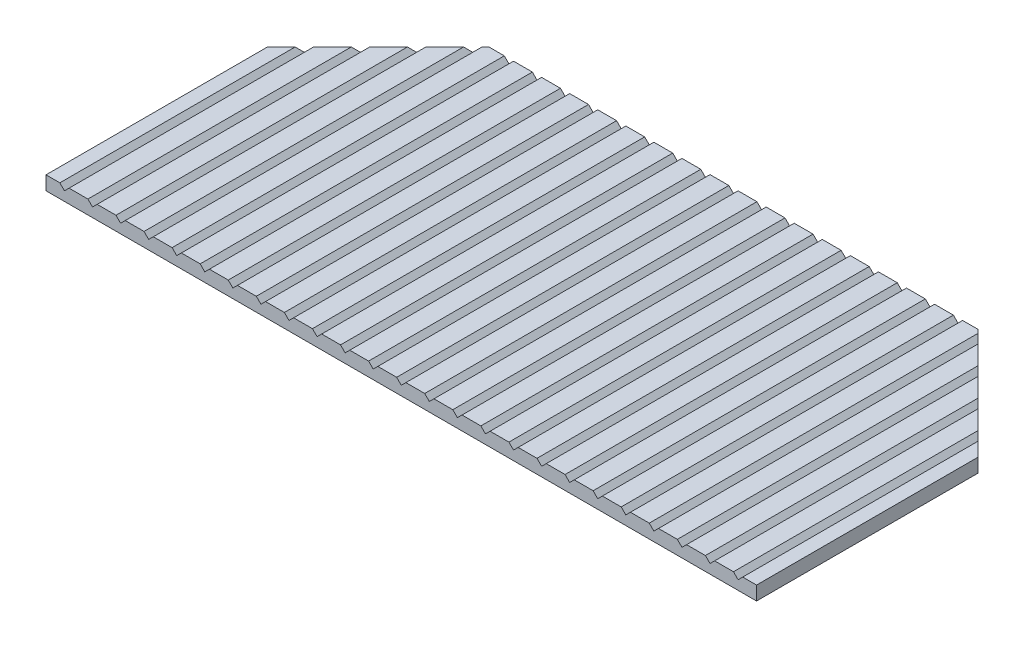
SolidWorks part; units mm, degrees
ref_plane "Front Plane" through (0, 0, 0) normal (0, 0, 1) x (1, 0, 0)
ref_plane "Top Plane" through (0, 0, 0) normal (0, 1, 0) x (1, 0, 0)
ref_plane "Right Plane" through (0, 0, 0) normal (1, 0, 0) x (0, 0, -1)
sketch "Sketch1" plane through (0, 0, 0) normal (0, 1, 0) x (1, 0, 0)
  line L0 (-38.5, 8.0676) -> (-26.5, 20.0676)
  line L1 (-26.5, 20.0676) -> (26.5, 20.0676)
  line L2 (-38.5, 8.0676) -> (-38.5, -15.9324)
  line L3 (-38.5, -15.9324) -> (38.5, -15.9324)
  line L4 (38.5, 8.0676) -> (38.5, -15.9324)
  line L5 (0, 0) -> (0, 23.6572) construction
  line L6 (38.5, 8.0676) -> (26.5, 20.0676)
  point P0 (0, 0)
  dimension "D1" = 77
  dimension "D2" = 36
  dimension "D3" = 12
  dimension "D4" = 8.0676
extrude "Boss-Extrude1" add sketch "Sketch1" along normal blind 1.5
sketch "Sketch2" plane through (0, 1.5, 0) normal (0, 1, 0) x (1, 0, 0)
  line L0 (-38.5, -15.9324) -> (38.5, -15.9324) construction
  line L1 (-37, -15.9324) -> (-36, -15.9324)
  line L2 (-37, -15.9324) -> (-37, 20.0676)
  line L3 (-37, 20.0676) -> (-36, 20.0676)
  line L4 (-36, -15.9324) -> (-36, 20.0676)
  line L5 (-38.5, 8.0676) -> (-38.5, -15.9324) construction
  line L6 (-32.9583, -15.9324) -> (-32.9583, 20.0676)
  line L7 (-33.9583, -15.9324) -> (-33.9583, 20.0676)
  line L8 (-33.9583, 20.0676) -> (-32.9583, 20.0676)
  line L9 (-33.9583, -15.9324) -> (-32.9583, -15.9324)
  line L10 (-29.9167, -15.9324) -> (-29.9167, 20.0676)
  line L11 (-30.9167, -15.9324) -> (-30.9167, 20.0676)
  line L12 (-30.9167, 20.0676) -> (-29.9167, 20.0676)
  line L13 (-30.9167, -15.9324) -> (-29.9167, -15.9324)
  line L14 (-26.875, -15.9324) -> (-26.875, 20.0676)
  line L15 (-27.875, -15.9324) -> (-27.875, 20.0676)
  line L16 (-27.875, 20.0676) -> (-26.875, 20.0676)
  line L17 (-27.875, -15.9324) -> (-26.875, -15.9324)
  line L18 (-23.8333, -15.9324) -> (-23.8333, 20.0676)
  line L19 (-24.8333, -15.9324) -> (-24.8333, 20.0676)
  line L20 (-24.8333, 20.0676) -> (-23.8333, 20.0676)
  line L21 (-24.8333, -15.9324) -> (-23.8333, -15.9324)
  line L22 (-20.7917, -15.9324) -> (-20.7917, 20.0676)
  line L23 (-21.7917, -15.9324) -> (-21.7917, 20.0676)
  line L24 (-21.7917, 20.0676) -> (-20.7917, 20.0676)
  line L25 (-21.7917, -15.9324) -> (-20.7917, -15.9324)
  line L26 (-17.75, -15.9324) -> (-17.75, 20.0676)
  line L27 (-18.75, -15.9324) -> (-18.75, 20.0676)
  line L28 (-18.75, 20.0676) -> (-17.75, 20.0676)
  line L29 (-18.75, -15.9324) -> (-17.75, -15.9324)
  line L30 (-14.7083, -15.9324) -> (-14.7083, 20.0676)
  line L31 (-15.7083, -15.9324) -> (-15.7083, 20.0676)
  line L32 (-15.7083, 20.0676) -> (-14.7083, 20.0676)
  line L33 (-15.7083, -15.9324) -> (-14.7083, -15.9324)
  line L34 (-11.6667, -15.9324) -> (-11.6667, 20.0676)
  line L35 (-12.6667, -15.9324) -> (-12.6667, 20.0676)
  line L36 (-12.6667, 20.0676) -> (-11.6667, 20.0676)
  line L37 (-12.6667, -15.9324) -> (-11.6667, -15.9324)
  line L38 (-8.625, -15.9324) -> (-8.625, 20.0676)
  line L39 (-9.625, -15.9324) -> (-9.625, 20.0676)
  line L40 (-9.625, 20.0676) -> (-8.625, 20.0676)
  line L41 (-9.625, -15.9324) -> (-8.625, -15.9324)
  line L42 (-5.5833, -15.9324) -> (-5.5833, 20.0676)
  line L43 (-6.5833, -15.9324) -> (-6.5833, 20.0676)
  line L44 (-6.5833, 20.0676) -> (-5.5833, 20.0676)
  line L45 (-6.5833, -15.9324) -> (-5.5833, -15.9324)
  line L46 (-2.5417, -15.9324) -> (-2.5417, 20.0676)
  line L47 (-3.5417, -15.9324) -> (-3.5417, 20.0676)
  line L48 (-3.5417, 20.0676) -> (-2.5417, 20.0676)
  line L49 (-3.5417, -15.9324) -> (-2.5417, -15.9324)
  line L50 (0.5, -15.9324) -> (0.5, 20.0676)
  line L51 (-0.5, -15.9324) -> (-0.5, 20.0676)
  line L52 (-0.5, 20.0676) -> (0.5, 20.0676)
  line L53 (-0.5, -15.9324) -> (0.5, -15.9324)
  line L54 (3.5417, -15.9324) -> (3.5417, 20.0676)
  line L55 (2.5417, -15.9324) -> (2.5417, 20.0676)
  line L56 (2.5417, 20.0676) -> (3.5417, 20.0676)
  line L57 (2.5417, -15.9324) -> (3.5417, -15.9324)
  line L58 (6.5833, -15.9324) -> (6.5833, 20.0676)
  line L59 (5.5833, -15.9324) -> (5.5833, 20.0676)
  line L60 (5.5833, 20.0676) -> (6.5833, 20.0676)
  line L61 (5.5833, -15.9324) -> (6.5833, -15.9324)
  line L62 (9.625, -15.9324) -> (9.625, 20.0676)
  line L63 (8.625, -15.9324) -> (8.625, 20.0676)
  line L64 (8.625, 20.0676) -> (9.625, 20.0676)
  line L65 (8.625, -15.9324) -> (9.625, -15.9324)
  line L66 (12.6667, -15.9324) -> (12.6667, 20.0676)
  line L67 (11.6667, -15.9324) -> (11.6667, 20.0676)
  line L68 (11.6667, 20.0676) -> (12.6667, 20.0676)
  line L69 (11.6667, -15.9324) -> (12.6667, -15.9324)
  line L70 (15.7083, -15.9324) -> (15.7083, 20.0676)
  line L71 (14.7083, -15.9324) -> (14.7083, 20.0676)
  line L72 (14.7083, 20.0676) -> (15.7083, 20.0676)
  line L73 (14.7083, -15.9324) -> (15.7083, -15.9324)
  line L74 (18.75, -15.9324) -> (18.75, 20.0676)
  line L75 (17.75, -15.9324) -> (17.75, 20.0676)
  line L76 (17.75, 20.0676) -> (18.75, 20.0676)
  line L77 (17.75, -15.9324) -> (18.75, -15.9324)
  line L78 (21.7917, -15.9324) -> (21.7917, 20.0676)
  line L79 (20.7917, -15.9324) -> (20.7917, 20.0676)
  line L80 (20.7917, 20.0676) -> (21.7917, 20.0676)
  line L81 (20.7917, -15.9324) -> (21.7917, -15.9324)
  line L82 (24.8333, -15.9324) -> (24.8333, 20.0676)
  line L83 (23.8333, -15.9324) -> (23.8333, 20.0676)
  line L84 (23.8333, 20.0676) -> (24.8333, 20.0676)
  line L85 (23.8333, -15.9324) -> (24.8333, -15.9324)
  line L86 (27.875, -15.9324) -> (27.875, 20.0676)
  line L87 (26.875, -15.9324) -> (26.875, 20.0676)
  line L88 (26.875, 20.0676) -> (27.875, 20.0676)
  line L89 (26.875, -15.9324) -> (27.875, -15.9324)
  line L90 (30.9167, -15.9324) -> (30.9167, 20.0676)
  line L91 (29.9167, -15.9324) -> (29.9167, 20.0676)
  line L92 (29.9167, 20.0676) -> (30.9167, 20.0676)
  line L93 (29.9167, -15.9324) -> (30.9167, -15.9324)
  line L94 (33.9583, -15.9324) -> (33.9583, 20.0676)
  line L95 (32.9583, -15.9324) -> (32.9583, 20.0676)
  line L96 (32.9583, 20.0676) -> (33.9583, 20.0676)
  line L97 (32.9583, -15.9324) -> (33.9583, -15.9324)
  line L98 (37, -15.9324) -> (37, 20.0676)
  line L99 (36, -15.9324) -> (36, 20.0676)
  line L100 (36, 20.0676) -> (37, 20.0676)
  line L101 (36, -15.9324) -> (37, -15.9324)
  line L102 (38.5, -15.9324) -> (38.5, 8.0676) construction
  line L103 (26.5, 20.0676) -> (-26.5, 20.0676) construction
  dimension "D1" = 1.5
  dimension "D2" = 1
  dimension "D4" = 1.5
  dimension "D3" = 25
extrude "Cut-Extrude1" cut sketch "Sketch2" against normal blind 0.5
sketch "Sketch3" plane through (0, 0, 0) normal (0, -1, 0) x (1, 0, 0)
  line L5 (26.5, -20.0676) -> (-26.5, -20.0676) construction
  line L6 (-15, -0.0676) -> (15, -0.0676)
  line L7 (-15, -0.0676) -> (-15, -2.0676)
  line L8 (-15, -2.0676) -> (15, -2.0676)
  line L9 (15, -0.0676) -> (15, -2.0676)
  line L10 (-15, -0.0676) -> (15, -2.0676) construction
  line L11 (-15, -2.0676) -> (15, -0.0676) construction
  point P0 (0, 0)
  point P1 (0, -1.0676)
  dimension "D1" = 18
  dimension "D2" = 2
  dimension "D3" = 30
  dimension "D4" = 0
extrude "Boss-Extrude2" add sketch "Sketch3" along normal blind 2
chamfer "Chamfer1" distance 0.5 angle 45 50 edges at (36, 1, 2.6824) (32.9583, 1, 1.1615) (37, 1, 3.1824) (33.9583, 1, 1.6615) (30.9167, 1, 0.1407) (27.875, 1, -1.3801) (24.8333, 1, -2.0676) (21.7917, 1, -2.0676) (18.75, 1, -2.0676) (15.7083, 1, -2.0676) (29.9167, 1, -0.3593) (26.875, 1, -1.8801) (23.8333, 1, -2.0676) (20.7917, 1, -2.0676) (17.75, 1, -2.0676) (14.7083, 1, -2.0676) (11.6667, 1, -2.0676) (8.625, 1, -2.0676) (5.5833, 1, -2.0676) (2.5417, 1, -2.0676) (12.6667, 1, -2.0676) (9.625, 1, -2.0676) (6.5833, 1, -2.0676) (3.5417, 1, -2.0676) (0.5, 1, -2.0676) (-2.5417, 1, -2.0676) (-5.5833, 1, -2.0676) (-8.625, 1, -2.0676) (-11.6667, 1, -2.0676) (-14.7083, 1, -2.0676) (-17.75, 1, -2.0676) (-20.7917, 1, -2.0676) (-0.5, 1, -2.0676) (-3.5417, 1, -2.0676) (-6.5833, 1, -2.0676) (-9.625, 1, -2.0676) (-12.6667, 1, -2.0676) (-15.7083, 1, -2.0676) (-18.75, 1, -2.0676) (-21.7917, 1, -2.0676) (-24.8333, 1, -2.0676) (-27.875, 1, -1.3801) (-23.8333, 1, -2.0676) (-26.875, 1, -1.8801) (-29.9167, 1, -0.3593) (-30.9167, 1, 0.1407) (-33.9583, 1, 1.6615) (-32.9583, 1, 1.1615) (-36, 1, 2.6824) (-37, 1, 3.1824)
